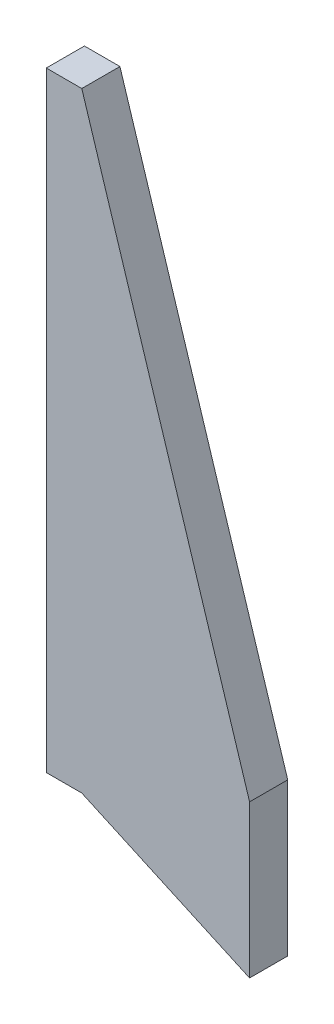
SolidWorks part; units mm, degrees
ref_plane "Front Plane" through (0, 0, 0) normal (0, 0, 1) x (1, 0, 0)
ref_plane "Top Plane" through (0, 0, 0) normal (0, 1, 0) x (1, 0, 0)
ref_plane "Right Plane" through (0, 0, 0) normal (1, 0, 0) x (0, 0, -1)
sketch "Sketch1" plane through (0, 0, 0) normal (0, 0, 1) x (1, 0, 0)
  line L0 (0, 0) -> (0, 80)
  line L1 (0, 80) -> (22, 10)
  line L2 (22, 10) -> (22, -10)
  line L3 (22, -10) -> (0, 0)
  dimension "D1" = 80
  dimension "D2" = 22
  dimension "D3" = 70
  dimension "D4" = 20
extrude "Boss-Extrude1" add sketch "Sketch1" along normal mid plane 5
sketch "Sketch7" plane through (0, 0, 0) normal (-1, 0, 0) x (0, 0, 1)
  line L4 (-2.5, 80) -> (-2.5, 0)
  line L5 (-2.5, 0) -> (2.5, 0)
  line L6 (2.5, 0) -> (2.5, 80)
  line L7 (2.5, 80) -> (-2.5, 80)
  line L8 (-2.5, 80) -> (-2.5, 0)
  line L9 (-2.5, 0) -> (2.5, 0)
  line L10 (2.5, 0) -> (2.5, 80)
  line L11 (2.5, 80) -> (-2.5, 80)
  dimension "D1" = 0
extrude "Boss-Extrude2" add sketch "Sketch7" along normal blind 4.655
